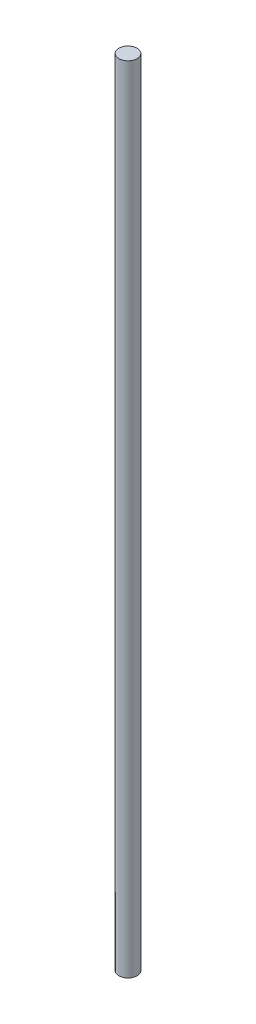
SolidWorks part; units mm, degrees
ref_plane "Front Plane" through (0, 0, 0) normal (0, 0, 1) x (1, 0, 0)
ref_plane "Top Plane" through (0, 0, 0) normal (0, 1, 0) x (1, 0, 0)
ref_plane "Right Plane" through (0, 0, 0) normal (1, 0, 0) x (0, 0, -1)
sketch "Sketch1" plane through (0, 0, 0) normal (0, 1, 0) x (1, 0, 0)
  circle A0 centre (0, 0) radius 4
  dimension "D1" = 8
extrude "Boss-Extrude1" add sketch "Sketch1" along normal blind 350
equation "\"Y-ROD-SPACING\"=75"
equation "\"Y-BED-OFFSET\"=2"
equation "\"Y-BED-ROD-INSET\"=3.5"
equation "\"T-SLOT-NUT-FILLET-RADIUS\"=0.5"
equation "\"T-SLOT-SCREW-SHAFT-RADIUS\"=1.55"
equation "\"T-SLOT-SCREW-SHAFT-CUTOUT-LENGTH\"=11"
equation "\"T-SLOT-NUT-DEPTH\"=3.5"
equation "\"T-SLOT-NUT-WIDTH\"=2.85"
equation "\"T-SLOT-NUT-END-DISTANCE\"=8"
equation "\"ACRYLIC-THICKNESS\"=10"
equation "\"ACRYLIC-TAB-CUTOUT-SIZE\"=\"ACRYLIC-THICKNESS\"+\"ACRYLIC-TAB-TOLERANCE\"*2"
equation "\"ACRYLIC-TAB-WIDTH\"=\"ACRYLIC-THICKNESS\""
equation "\"ACRYLIC-M3-HOLE\"=2.9"
equation "\"SMOOTHROD-CAP-SCREW-DISTANCE\"=20"
equation "\"FRAME-WIDTH-INNER\"=370"
equation "\"NEMA17-HOLE-SPACING\"=31"
equation "\"NEMA17-CENTRAL-CUTOUT\"=22.5"
equation "\"Z-BRACKET-REACH\"=55"
equation "\"TOP-BRACKET-SPACING\"=40"
equation "\"SMOOTHROD-X-LENGTH\"=350"
equation "\"SMOOTHROD-Y-LENGTH\"=350"
equation "\"SMOOTHROD-Z-LENGTH\"=350"
equation "\"SMOOTHROD-TIGHTENING-HEADROOM\"=.25"
equation "\"LEADSCREW-Z-LENGTH\"=300"
equation "\"D1@Boss-Extrude1\"=\"SMOOTHROD-Z-LENGTH\""
